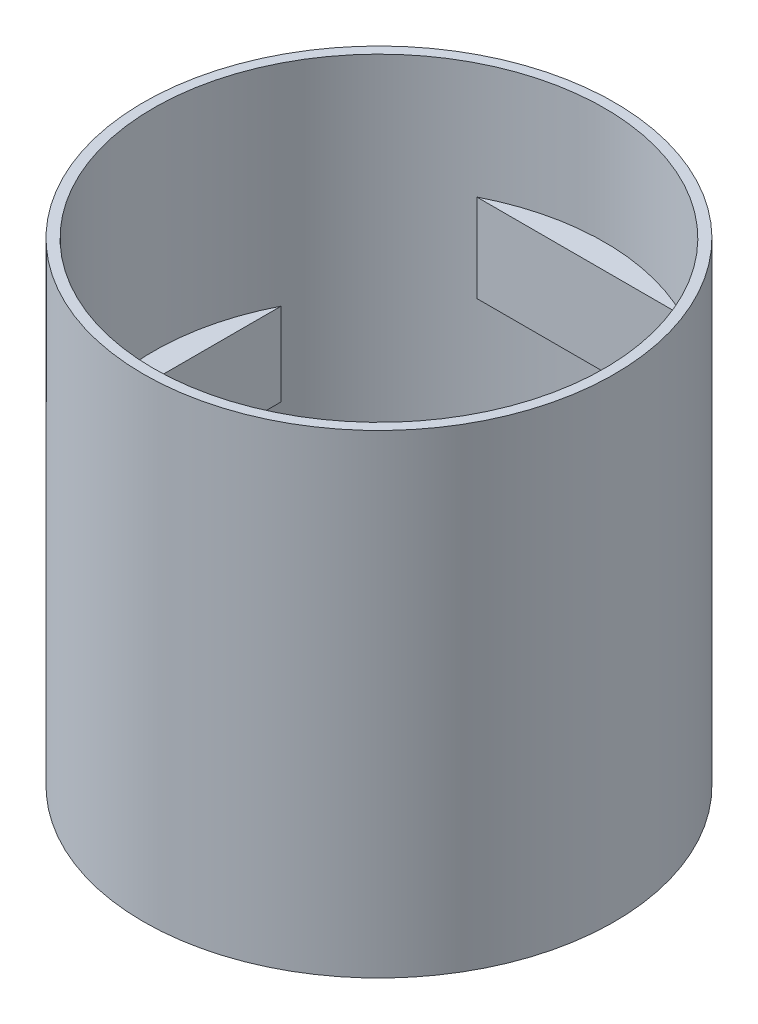
SolidWorks part; units mm, degrees
ref_plane "前基準面" through (0, 0, 0) normal (0, 0, 1) x (1, 0, 0)
ref_plane "上基準面" through (0, 0, 0) normal (0, 1, 0) x (1, 0, 0)
ref_plane "右基準面" through (0, 0, 0) normal (1, 0, 0) x (0, 0, -1)
sketch "草圖1" plane through (0, 0, 0) normal (0, 1, 0) x (1, 0, 0)
  line L0 (0, 78.355) -> (0, -92.3476) construction
  line L1 (-97.6496, 0) -> (95.3358, 0) construction
  line L3 (-34, 34) -> (34, 34) construction
  line L4 (-34, 34) -> (-34, -34) construction
  line L5 (-34, -34) -> (34, -34) construction
  line L6 (34, 34) -> (34, -34) construction
  line L7 (-34, 34) -> (34, -34) construction
  line L20 (45.5449, 45.5449) -> (-45.5449, -45.5449) construction
  circle A0 centre (0, 0) radius 72.25
  circle A1 centre (0, 0) radius 71
  circle A2 centre (0, 0) radius 68
  circle A4 centre (0, 0) radius 73 construction
  point P7 (0, 0)
  point P12 (-30, 30)
  point P14 (30, 30)
  point P17 (30, -30)
  point P18 (-30, -30)
  point P19 (0, 0)
  point P23 (-73, 0)
  point P24 (-72.25, 0)
  point P25 (-71, 0)
  point P26 (34, 0)
  point P27 (-34, 0)
  point P28 (-68, 0)
  dimension "D1" = 144.5
  dimension "D5" = 142
  dimension "D6" = 3
  dimension "D8" = 146
  dimension "D2" = 68
  dimension "D3" = 4
  dimension "D4" = 4
sketch "草圖4" plane through (0, 0, 0) normal (0, 0, 1) x (1, 0, 0)
  line L0 (-34, 0) -> (-34, 143)
  line L1 (73, 0) -> (-73, 0) construction
  line L3 (34, 0) -> (37.1213, 143)
  line L4 (37.1213, 143) -> (-34, 143)
  line L5 (-34, 0) -> (34, 0)
  line L6 (-34, 15) -> (34.3274, 15)
  line L7 (-34, 16.5) -> (34.3601, 16.5)
  line L8 (-34, 36.5) -> (34.7967, 36.5)
  line L9 (-34, 38) -> (34.8294, 38)
  line L10 (-34, 53) -> (35.1568, 53)
  line L11 (-34, 54.5) -> (35.1896, 54.5)
  line L12 (-34, 81.5) -> (35.7789, 81.5)
  line L13 (-34, 83) -> (35.8117, 83)
  line L14 (-34, 108) -> (36.3573, 108)
  line L15 (-34, 110) -> (36.401, 110)
  line L16 (-34, 126.5) -> (36.7611, 126.5)
  line L17 (-34, 128) -> (36.7939, 128)
  line L18 (-72.25, 0) -> (-72.25, 145.0993)
  line L19 (-68, 0) -> (-68, 146.8435)
  line L20 (-30, 0) -> (-30, 170.404) construction
  line L21 (-31.5, 143) -> (-31.5, 149) construction
  line L22 (-31.5, 149) -> (-28.5, 149) construction
  line L23 (-28.5, 149) -> (-28.5, 143) construction
  line L24 (-34, 111.5) -> (36.4337, 111.5)
  line L25 (-34, 79.5) -> (35.7353, 79.5)
  point P40 (-30, 149)
  dimension "D1" = 1.5
  dimension "D2" = 15
  dimension "D3" = 1.5
  dimension "D4" = 1.5
  dimension "D5" = 1.5
  dimension "D6" = 20
  dimension "D7" = 15
  dimension "D8" = 25
  dimension "D9" = 2
  dimension "D10" = 25
  dimension "D11" = 1.5
  dimension "D12" = 15
  dimension "D13" = 15
  dimension "D14" = 3
  dimension "D15" = 6
  dimension "D16" = 1.5
  dimension "D17" = 108
  dimension "D18" = 2
sketch "草圖5" plane through (0, 0, 0) normal (0, 1, 0) x (1, 0, 0)
  line L0 (-60.5191, 11) -> (-50.0191, 11) construction
  line L1 (-50.0191, 11) -> (-50.0191, -11) construction
  line L2 (-50.0191, -11) -> (-60.5191, -11) construction
  line L3 (-60.5191, -11) -> (-60.5191, 11)
  line L4 (-60.5191, 8.25) -> (-70.5191, 8.25) construction
  line L6 (-70.5191, -8.25) -> (-60.5191, -8.25) construction
  line L7 (-97.6496, 0) -> (95.3358, 0) construction
  line L8 (-60.5191, 8.25) -> (-60.5191, -8.25) construction
  line L9 (-34, 34) -> (34, -34) construction
  line L10 (0, 0) -> (-19.3715, 0) construction
  line L12 (-70.5191, 8.25) -> (-70.5191, -8.25) construction
  line L13 (-60.5191, 8.25) -> (-60.5191, 31.0072)
  line L14 (-60.5191, -8.25) -> (-60.5191, -31.0072)
  line L15 (8.25, 60.5191) -> (8.25, 70.5191) construction
  line L16 (-8.25, 70.5191) -> (-8.25, 60.5191) construction
  line L17 (8.25, 60.5191) -> (31.0072, 60.5191)
  line L18 (-8.25, 60.5191) -> (-31.0072, 60.5191)
  line L19 (11, 60.5191) -> (11, 50.0191) construction
  line L20 (11, 50.0191) -> (-11, 50.0191) construction
  line L21 (-11, 50.0191) -> (-11, 60.5191) construction
  line L22 (-11, 60.5191) -> (11, 60.5191)
  line L23 (8.25, 60.5191) -> (-8.25, 60.5191) construction
  line L24 (8.25, 70.5191) -> (-8.25, 70.5191) construction
  line L25 (60.5191, -8.25) -> (70.5191, -8.25) construction
  line L26 (70.5191, 8.25) -> (60.5191, 8.25) construction
  line L27 (60.5191, -8.25) -> (60.5191, -31.0072)
  line L28 (60.5191, 8.25) -> (60.5191, 31.0072)
  line L29 (60.5191, -11) -> (50.0191, -11) construction
  line L30 (50.0191, -11) -> (50.0191, 11) construction
  line L31 (50.0191, 11) -> (60.5191, 11) construction
  line L32 (60.5191, 11) -> (60.5191, -11)
  line L33 (60.5191, -8.25) -> (60.5191, 8.25) construction
  line L34 (70.5191, -8.25) -> (70.5191, 8.25) construction
  line L35 (-8.25, -60.5191) -> (-8.25, -70.5191) construction
  line L36 (8.25, -70.5191) -> (8.25, -60.5191) construction
  line L37 (-8.25, -60.5191) -> (-31.0072, -60.5191)
  line L38 (8.25, -60.5191) -> (31.0072, -60.5191)
  line L39 (-11, -60.5191) -> (-11, -50.0191) construction
  line L40 (-11, -50.0191) -> (11, -50.0191) construction
  line L41 (11, -50.0191) -> (11, -60.5191) construction
  line L42 (11, -60.5191) -> (-11, -60.5191)
  line L43 (-8.25, -60.5191) -> (8.25, -60.5191) construction
  line L44 (-8.25, -70.5191) -> (8.25, -70.5191) construction
  circle A0 centre (0, 0) radius 68 construction
  circle A1 centre (0, 0) radius 72.25 construction
  arc A2 (-31.0072, 60.5191) -> (-60.5191, 31.0072) centre (0, 0) ccw
  circle A3 centre (0, 0) radius 68
  arc A5 (-60.5191, -31.0072) -> (-31.0072, -60.5191) centre (0, 0) ccw
  circle A6 centre (0, 0) radius 72.25
  arc A7 (60.5191, 31.0072) -> (31.0072, 60.5191) centre (0, 0) ccw
  circle A8 centre (0, 0) radius 71 construction
  circle A9 centre (0, 0) radius 71
  arc A12 (31.0072, -60.5191) -> (60.5191, -31.0072) centre (0, 0) ccw
  point P7 (-60.5191, 0)
  point P26 (65.5191, 8.25)
  point P58 (0, 0)
  dimension "D1" = 10
  dimension "D2" = 10.5
  dimension "D3" = 22
  dimension "D4" = 16.5
  dimension "D5" = 4
extrude "填料-伸長1" add sketch "草圖1" along normal up to vertex (143 mm away) contours A1 A2 region at (-68.9918, 0, 0) up to point (-34, 143, 0)
sketch "草圖15" plane through (0, 0, 0) normal (0, -1, 0) x (1, 0, 0)
  circle A0 centre (-30, 30) radius 1.5
  circle A1 centre (-30, 30) radius 3
  dimension "D1" = 3
  dimension "D2" = 6
sketch "草圖16" plane through (0, 0, 0) normal (0, -1, 0) x (-1, 0, 0)
  line L1 (-53.8073, 26.6906) -> (-37.8073, 26.6906)
  line L2 (-53.8073, 26.6906) -> (-53.8073, 14.4906)
  line L3 (-53.8073, 14.4906) -> (-37.8073, 14.4906)
  line L4 (-37.8073, 26.6906) -> (-37.8073, 14.4906)
  line L5 (-53.8073, 26.6906) -> (-37.8073, 14.4906) construction
  line L6 (-53.8073, 14.4906) -> (-37.8073, 26.6906) construction
  line L7 (-54.8073, 27.6906) -> (-36.8073, 27.6906)
  line L8 (-54.8073, 27.6906) -> (-54.8073, 13.4906)
  line L9 (-54.8073, 13.4906) -> (-36.8073, 13.4906)
  line L10 (-36.8073, 27.6906) -> (-36.8073, 13.4906)
  line L11 (-54.8073, 27.6906) -> (-36.8073, 13.4906) construction
  line L12 (-54.8073, 13.4906) -> (-36.8073, 27.6906) construction
  point P0 (-45.8073, 20.5906)
  point P5 (-45.8073, 20.5906)
  point P10 (0.2588, 21.0877)
  point P11 (-14.9287, 17.3402)
  point P12 (-10.6335, 20.6153)
  dimension "D1" = 16
  dimension "D2" = 12.2
  dimension "D3" = 1
  dimension "D4" = 1
  dimension "D5" = 1
  dimension "D6" = 1
sketch "草圖17" plane through (0, 0, 0) normal (0, -1, 0) x (-1, 0, 0)
  circle A0 centre (-41.8475, 42.297) radius 8.5
  circle A1 centre (0, 0) radius 68 construction
  point P2 (-23.6885, 37.369)
  point P3 (-34.7702, 46.8957)
  point P4 (-41.5026, 41.9484)
  dimension "D1" = 17
extrude "填料-伸長8" add sketch "草圖5" along normal up to vertex (79.5 mm away) from vertex contours L13 A3 L14 L3 | L27 A3 L28 L32 region at (-63.526, 0, 0) region at (63.526, 0, 0) up to point (-34, 79.5, 0) starting at point (-34, 54.5, 0)
extrude "填料-伸長9" add sketch "草圖5<10>" along normal up to vertex (108 mm away) from vertex contours L37 A3 L38 L42 | L17 A3 L18 L22 region at (0, 0, 63.526) region at (0, 0, -63.526) up to point (36.3573, 108, 0) starting at point (35.7789, 81.5, 0)
sketch "草圖5<10>" plane through (0, 0, 0) normal (0, 1, 0) x (1, 0, 0) same geometry as "草圖5"
